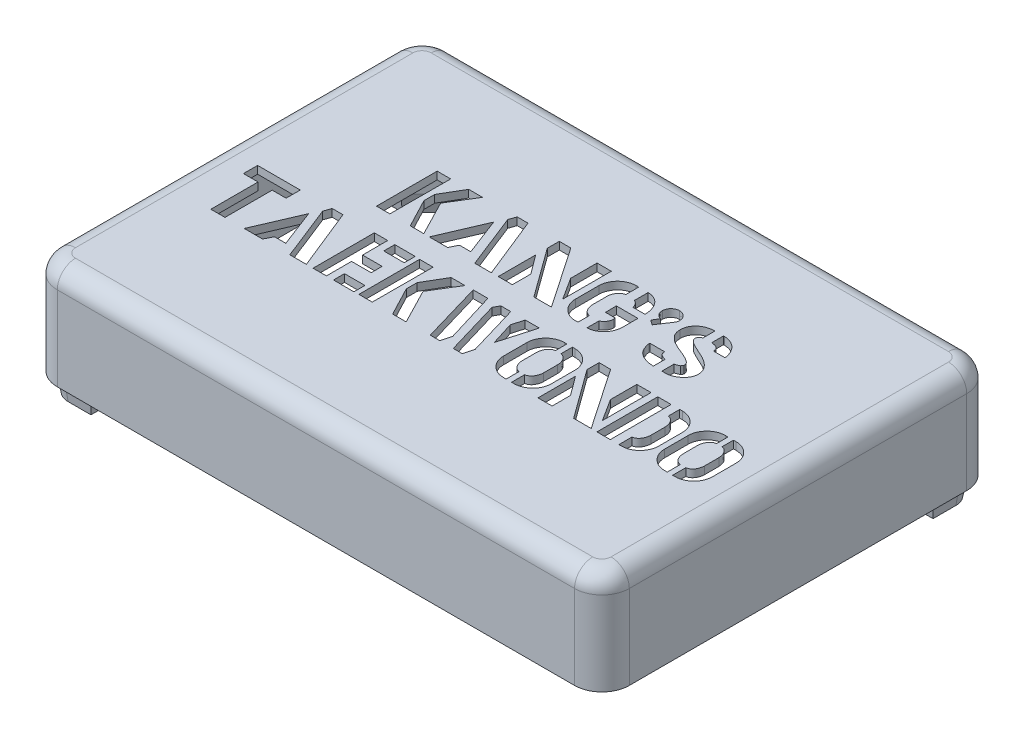
SolidWorks part; units mm, degrees
ref_plane "Front Plane" through (0, 0, 0) normal (0, 0, 1) x (1, 0, 0)
ref_plane "Top Plane" through (0, 0, 0) normal (0, 1, 0) x (1, 0, 0)
ref_plane "Right Plane" through (0, 0, 0) normal (1, 0, 0) x (0, 0, -1)
sketch "Sketch1" plane through (0, 0, 0) normal (0, 1, 0) x (1, 0, 0)
  line L0 (-41.5, -30.5958) -> (-41.5, 24.85)
  line L1 (-37, -33.5958) -> (48, -33.5958)
  line L2 (-40, -30.5958) -> (-40, 24.85)
  line L3 (-37, 27.85) -> (48, 27.85)
  line L4 (51, -30.5958) -> (51, 24.85)
  line L5 (-40, -33.5958) -> (51, 27.85) construction
  line L6 (-40, 27.85) -> (51, -33.5958) construction
  line L7 (-37, 29.35) -> (48, 29.35)
  line L8 (52.5, -30.5958) -> (52.5, 24.85)
  line L9 (-37, -35.0958) -> (48, -35.0958)
  line L12 (-37, 29.35) -> (48, 29.35) construction
  line L13 (48, -35.0958) -> (-37, -35.0958) construction
  line L14 (52.5, 24.85) -> (52.5, -30.5958) construction
  line L15 (-41.5, -30.5958) -> (-41.5, 24.85) construction
  arc A0 (48, -33.5958) -> (51, -30.5958) centre (48, -30.5958) ccw
  arc A1 (-37, -33.5958) -> (-40, -30.5958) centre (-37, -30.5958) cw
  arc A2 (-40, 24.85) -> (-37, 27.85) centre (-37, 24.85) cw
  arc A3 (48, 27.85) -> (51, 24.85) centre (48, 24.85) cw
  arc A4 (-41.5, 24.85) -> (-37, 29.35) centre (-37, 24.85) cw
  arc A5 (48, 29.35) -> (52.5, 24.85) centre (48, 24.85) cw
  arc A6 (48, -35.0958) -> (52.5, -30.5958) centre (48, -30.5958) ccw
  arc A7 (-37, -35.0958) -> (-41.5, -30.5958) centre (-37, -30.5958) cw
  dimension "D1" = 3
  dimension "D2" = 1.5
extrude "Boss-Extrude1" add sketch "Sketch1" along normal blind 1.25 contours A7 L9 A6 L8 A5 L7 A4 L0 L3 A3 L4 A0 L1 A1 L2 A2 | A3 L3 A2 L2 A1 L1 A0 L4 region at (-40.3603, 0, 2.8729) region at (5.5, 0, 2.8729)
extrude "Boss-Extrude2" add sketch "Sketch1<3>" against normal up to surface (15.5512 mm away)
sketch "Sketch1<3>" plane through (0, 0, 0) normal (0, 1, 0) x (1, 0, 0) same geometry as "Sketch1"
sketch "Sketch2" plane through (0, 0, -29.35) normal (0, 0, -1) x (-1, 0, 0)
  line L5 (25.025, -2.0212) -> (-19.705, -2.0212)
  line L6 (25.025, -2.0212) -> (25.025, -15.5512)
  line L7 (25.025, -15.5512) -> (-19.705, -15.5512)
  line L30 (-19.705, -2.0212) -> (-19.705, -15.5512)
  line L32 (-48, -15.5512) -> (37, -15.5512) construction
  line L34 (-40.025, -15.5512) -> (-25.775, -15.5512)
  line L35 (-40.025, -15.5512) -> (-40.025, -2.0212)
  line L36 (24.525, -3.0212) -> (11.275, -3.0212) construction
  line L38 (-40.025, -2.0212) -> (-25.775, -2.0212)
  line L39 (-25.775, -15.5512) -> (-25.775, -2.0212)
  dimension "D2" = 1
  dimension "D3" = 0.5
  dimension "D4" = 0.5
  dimension "D5" = 0.5
  dimension "D1" = 0.5
extrude "Cut-Extrude1" cut sketch "Sketch2" against normal up to next
sketch "Sketch3" plane through (0, 0, 0) normal (0, -1, 0) x (1, 0, 0)
  line L0 (-32.7145, -24.1) -> (-36.25, -20.5645)
  line L1 (-36.25, 26.3103) -> (-32.7145, 29.8458)
  line L2 (43.7145, -24.1) -> (47.25, -20.5645)
  line L3 (48, -28.1) -> (43.7145, -28.1)
  line L4 (43.7145, -28.1) -> (43.7145, -24.1)
  line L5 (51.25, -24.85) -> (51.25, -20.5645)
  line L6 (51.25, -20.5645) -> (47.25, -20.5645)
  line L7 (-37, -28.1) -> (-32.7145, -28.1)
  line L8 (-32.7145, -28.1) -> (-32.7145, -24.1)
  line L9 (-40.25, -24.85) -> (-40.25, -20.5645)
  line L10 (-40.25, -20.5645) -> (-36.25, -20.5645)
  line L11 (-40.25, 30.5958) -> (-40.25, 26.3103)
  line L12 (-40.25, 26.3103) -> (-36.25, 26.3103)
  line L13 (-32.7145, 29.8458) -> (-32.7145, 33.8458)
  line L14 (-32.7145, 33.8458) -> (-37, 33.8458)
  arc A0 (51.25, -24.85) -> (48, -28.1) centre (48, -24.85) cw
  arc A1 (48, -27.85) -> (51, -24.85) centre (48, -24.85) ccw construction
  arc A3 (-37, -28.1) -> (-40.25, -24.85) centre (-37, -24.85) cw
  arc A4 (-40, -24.85) -> (-37, -27.85) centre (-37, -24.85) ccw construction
  arc A5 (-40.25, 30.5958) -> (-37, 33.8458) centre (-37, 30.5958) cw
  arc A6 (-37, 33.5958) -> (-40, 30.5958) centre (-37, 30.5958) ccw construction
  dimension "D1" = 0.25
  dimension "D2" = 5
  dimension "D3" = 4
extrude "Boss-Extrude3" add sketch "Sketch3" along normal up to surface (15.5512 mm away) up to face at (5.9, -15.5512, -3.4217)
extrude "Boss-Extrude4" add sketch "Sketch3<3>" along normal blind 3 draft 10 from surface starting at face at (22.74, -15.5512, -28.6)
sketch "Sketch3<3>" plane through (0, 0, 0) normal (0, -1, 0) x (1, 0, 0) same geometry as "Sketch3"
fillet "Fillet1" radius 3 22 edges at (-40.182, 1.25, -28.032) (-41.5, 1.25, 2.8729) (-40.182, 1.25, 33.7778) (5.5, 1.25, 35.0958) (51.182, 1.25, 33.7778) (52.5, 1.25, 2.8729) (51.182, 1.25, -28.032) (5.5, 1.25, -29.35) (-40, 0, 2.8729) (5.5, 0, -27.85) (51, 0, 5.0157) (50.1213, 0, 32.7171) (7.6428, 0, 33.5958) (-32.7145, 0, -25.975) (-34.4822, 0, -22.3322) (-38.125, 0, -20.5645) (-38.125, 0, 26.3103) (-34.4822, 0, 28.078) (-32.7145, 0, 31.7208) (49.125, 0, -20.5645) (45.4822, 0, -22.3322) (43.7145, 0, -25.975)
sketch "Sketch4" plane through (0, -15.5512, 0) normal (0, -1, 0) x (1, 0, 0)
  line L0 (48, -29.35) -> (40.025, -29.35) construction
  line L1 (37.6139, -29.35) -> (46.45, -29.35)
  line L2 (37.6139, -29.35) -> (37.6139, -21.3645)
  line L3 (37.6139, -21.3645) -> (46.45, -21.3645)
  line L4 (46.45, -29.35) -> (46.45, -21.3645)
  line L6 (47.25, -20.5645) -> (43.7145, -24.1) construction
  line L10 (45.95, -27.85) -> (45.95, -17.0042) construction
  dimension "D1" = 0.5
extrude "Cut-Extrude2" cut sketch "Sketch4" along normal through all
sketch "Sketch5" plane through (0, 1.25, 0) normal (0, 1, 0) x (1, 0, 0)
  line L0 (-38.5, 0) -> (49.5, 0) construction
  line L1 (-38.5, -14) -> (49.5, -14) construction
  line L2 (-38.5, 24.85) -> (-38.5, -30.5958) construction
  line L3 (49.5, -30.5958) -> (49.5, 24.85) construction
  text T0 "KANG'S" font "Stencil Gothic" height 10
  text T1 "TAEKWONDO" font "Stencil Gothic" height 10
  dimension "D1" = 14
extrude "Cut-Extrude3" cut sketch "Sketch5" against normal through all
